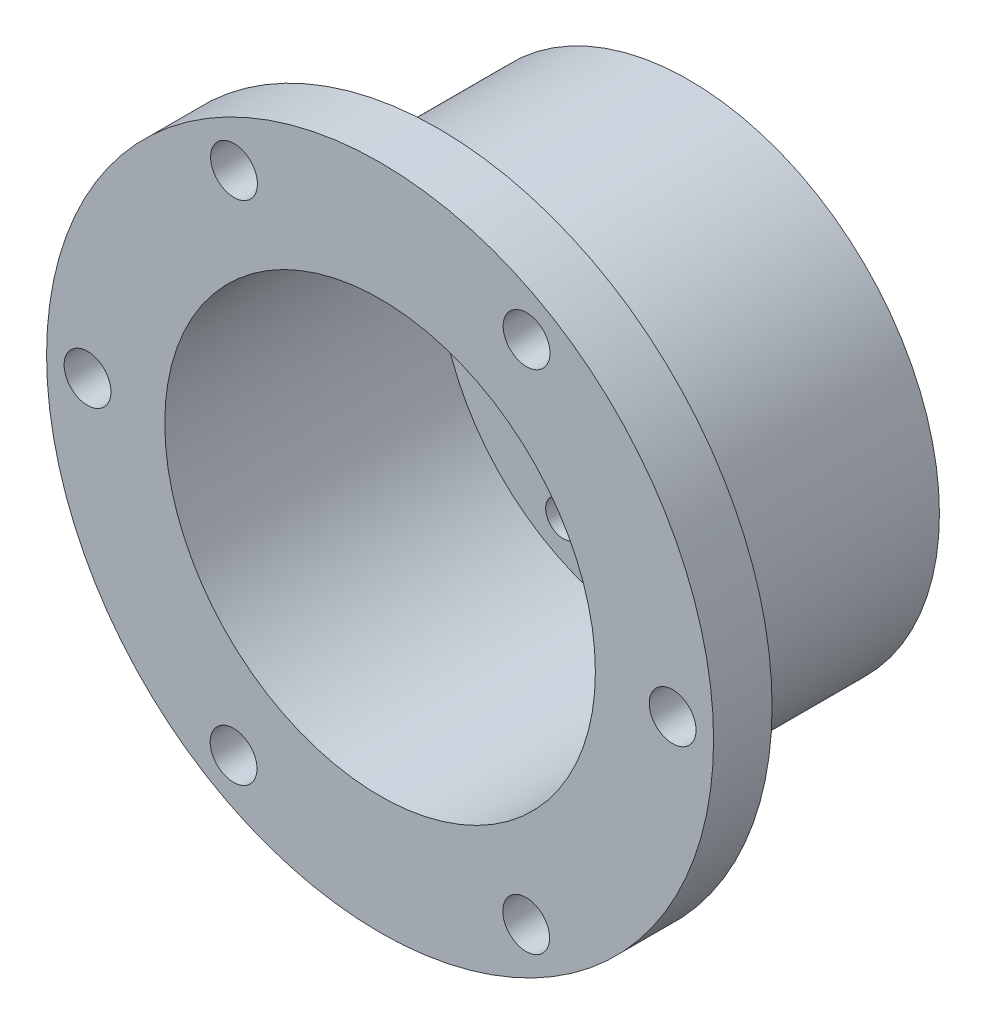
SolidWorks part; units mm, degrees
material "Resina de melamina"
ref_plane "Alzado" through (0, 0, 0) normal (0, 0, 1) x (1, 0, 0)
ref_plane "Planta" through (0, 0, 0) normal (0, 1, 0) x (1, 0, 0)
ref_plane "Vista lateral" through (0, 0, 0) normal (1, 0, 0) x (0, 0, -1)
sketch "Croquis1" plane through (0, 0, 0) normal (0, 0, 1) x (1, 0, 0)
  circle A0 centre (0, 0) radius 18.4
  circle A1 centre (0, 0) radius 21.4
  dimension "D1" = 36.8
  dimension "D2" = 42.8
extrude "Saliente-Extruir1" add sketch "Croquis1" along normal blind 26.4
sketch "Croquis2" plane through (0, 0, 0) normal (0, 0, -1) x (-1, 0, 0)
  circle A0 centre (0, 0) radius 18.65
  dimension "D1" = 37.3
extrude "Saliente-Extruir2" add sketch "Croquis2" against normal blind 3
sketch "Croquis3" plane through (0, 0, 26.4) normal (0, 0, 1) x (1, 0, 0)
  circle A0 centre (0, 0) radius 21.4
  circle A1 centre (0, 0) radius 28.5
  dimension "D1" = 57
extrude "Saliente-Extruir3" add sketch "Croquis3" against normal blind 5
sketch "Croquis4" plane through (0, 0, 0) normal (0, 0, -1) x (-1, 0, 0)
  line L0 (0, 0) -> (0, -7) construction
  line L1 (-13, 0) -> (-14, 0) construction
  line L2 (-14, 0) -> (-17, 0) construction
  circle A0 centre (0, -7) radius 6
  circle A9 centre (-15.5, 0) radius 1.5
  circle A10 centre (-7.75, 13.4234) radius 1.5
  circle A11 centre (7.75, 13.4234) radius 1.5
  circle A12 centre (15.5, 0) radius 1.5
  circle A13 centre (7.75, -13.4234) radius 1.5
  circle A14 centre (-7.75, -13.4234) radius 1.5
  dimension "D2" = 12
  dimension "D1" = 7
  dimension "D3" = 1
  dimension "D4" = 3
  dimension "D5" = 6
extrude "Cortar-Extruir1" cut sketch "Croquis4" against normal blind 3
sketch "Croquis6" plane through (0, 0, 26.4) normal (0, 0, 1) x (1, 0, 0)
  line L0 (0, 0) -> (-7.75, 13.4234) construction
  line L1 (-7.75, 13.4234) -> (-9.1877, 15.942) construction
  line L2 (-9.1877, 15.942) -> (-14.2309, 24.6927) construction
  line L3 (-14.2309, 24.6927) -> (-12.4833, 21.6603) construction
  circle A0 centre (0, 0) radius 18.4 construction
  circle A1 centre (12.5167, 21.641) radius 2
  circle A8 centre (25, -0.0193) radius 2
  circle A9 centre (0, 0) radius 28.5 construction
  circle A10 centre (-12.4833, 21.6603) radius 2
  circle A16 centre (12.4833, -21.6603) radius 2
  circle A17 centre (-12.5167, -21.641) radius 2
  circle A18 centre (-25, 0.0193) radius 2
  dimension "D1" = 3.5
  dimension "D2" = 4
  dimension "D3" = 6
extrude "Cortar-Extruir2" cut sketch "Croquis6" against normal through all
